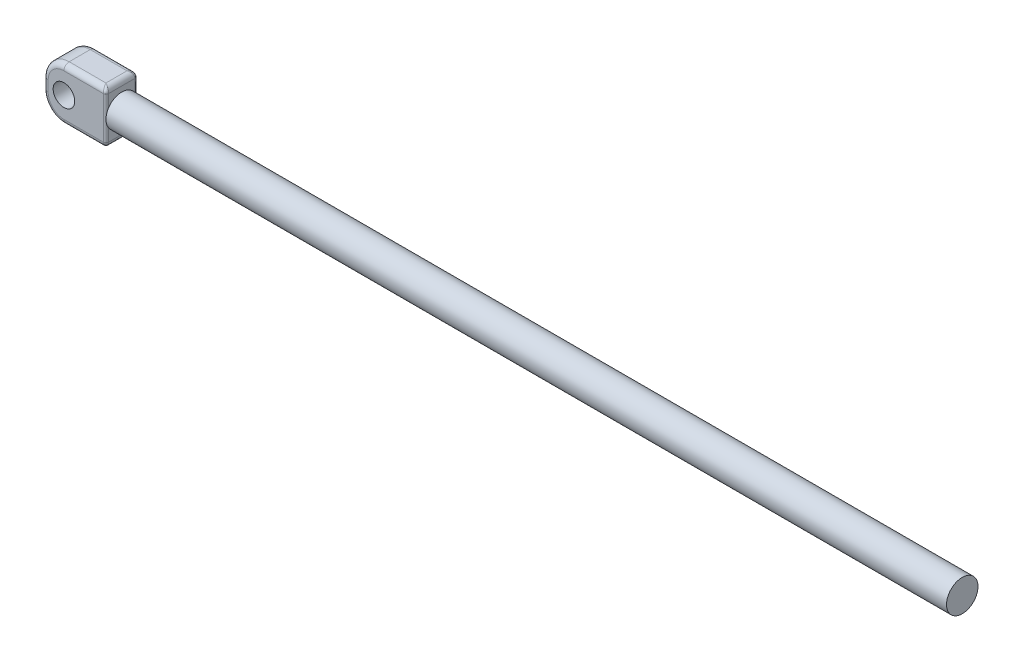
SolidWorks part; units mm, degrees
ref_plane "Front Plane" through (0, 0, 0) normal (0, 0, 1) x (1, 0, 0)
ref_plane "Top Plane" through (0, 0, 0) normal (0, 1, 0) x (1, 0, 0)
ref_plane "Right Plane" through (0, 0, 0) normal (1, 0, 0) x (0, 0, -1)
sketch "Sketch1" plane through (0, 0, 0) normal (0, 0, 1) x (1, 0, 0)
  line L0 (-250, 0) -> (250, 0) construction
  line L1 (250, 0) -> (250, 6)
  line L2 (250, 6) -> (-70, 6)
  line L3 (-70, 6) -> (-70, 0)
  line L4 (-70, 0) -> (250, 0)
  point P4 (0, 0)
  dimension "D1" = 500
  dimension "D2" = 320
  dimension "D3" = 6
revolve "Revolve1" add sketch "Sketch1" angle 360 about L0
sketch "Sketch2" plane through (0, 0, 0) normal (0, 0, 1) x (1, 0, 0)
  line L8 (-70, -10) -> (-70, 10)
  line L9 (-70, 10) -> (-86, 10)
  line L10 (-94, 2) -> (-94, -2)
  line L11 (-86, -10) -> (-70, -10)
  arc A0 (-86, 10) -> (-94, 2) centre (-86, 2) ccw
  arc A1 (-94, -2) -> (-86, -10) centre (-86, -2) ccw
  circle A2 centre (-86, 0) radius 4.1
  point P8 (-70, 0)
  point P13 (-94, 10)
  dimension "D3" = 8
  dimension "D4" = 8.2
  dimension "D5" = 8
  dimension "D7" = 70
  dimension "D1" = 20
  dimension "D2" = 24
  dimension "D6" = 10
extrude "Boss-Extrude1" add sketch "Sketch2" along normal mid plane 12 separate body
fillet "Fillet2" radius 1 2 edges at (-70, 0, -6) (-70, 0, 6)
fillet "Fillet3" radius 2 16 edges at (-70.2929, 10, 5.7071) (-78.5, 10, 6) (-91.6569, 7.6569, 6) (-94, 0, 6) (-91.6569, -7.6569, 6) (-78.5, -10, 6) (-70.2929, -10, 5.7071) (-70, -10, 0) (-70.2929, -10, -5.7071) (-78.5, -10, -6) (-91.6569, -7.6569, -6) (-94, 0, -6) (-91.6569, 7.6569, -6) (-78.5, 10, -6) (-70.2929, 10, -5.7071) (-70, 10, 0)
